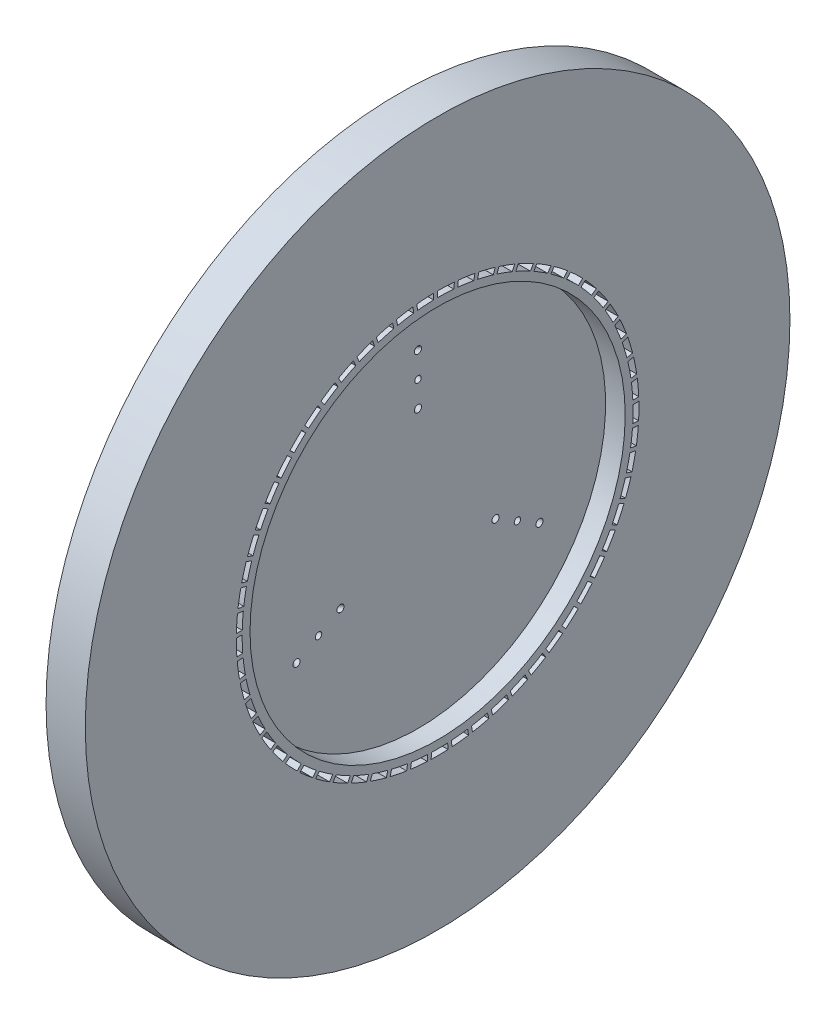
SolidWorks part; units mm, degrees
ref_plane "Front Plane" through (0, 0, 0) normal (0, 0, 1) x (1, 0, 0)
ref_plane "Top Plane" through (0, 0, 0) normal (0, 1, 0) x (1, 0, 0)
ref_plane "Right Plane" through (0, 0, 0) normal (1, 0, 0) x (0, 0, -1)
sketch "Sketch1" plane through (0, 0, 0) normal (1, 0, 0) x (0, 0, -1)
  circle A0 centre (0, 0) radius 89.825
  circle A5 centre (0, 0) radius 47.825
  dimension "D1" = 179.65
  dimension "D2" = 95.65
extrude "Flange" add sketch "Sketch1" along normal blind 10
sketch "Regen Slots Sketch" plane through (10, 0, 0) normal (1, 0, 0) x (0, 0, -1)
  line L0 (0, 49.825) -> (0, 51.325)
  line L1 (-1, 49.815) -> (-1, 51.3153)
  line L2 (5.1231, 49.5609) -> (5.2773, 51.053)
  line L3 (4.1273, 49.6538) -> (4.2816, 51.1461)
  line L4 (10.1918, 48.7715) -> (10.4986, 50.2398)
  line L5 (9.2109, 48.9662) -> (9.5178, 50.4348)
  line L6 (15.1525, 47.4651) -> (15.6087, 48.894)
  line L7 (14.1968, 47.7596) -> (14.6531, 49.1888)
  line L8 (19.9526, 45.6555) -> (20.5533, 47.03)
  line L9 (19.0323, 46.0467) -> (19.6331, 47.4215)
  line L10 (24.5412, 43.362) -> (25.28, 44.6674)
  line L11 (23.666, 43.8458) -> (24.4049, 45.1515)
  line L12 (28.8697, 40.6088) -> (29.7388, 41.8313)
  line L13 (28.0488, 41.18) -> (28.9181, 42.4028)
  line L14 (32.8921, 37.4251) -> (33.8823, 38.5518)
  line L15 (32.1343, 38.0778) -> (33.1247, 39.2047)
  line L16 (36.5658, 33.8448) -> (37.6667, 34.8637)
  line L17 (35.8792, 34.5719) -> (36.9802, 35.591)
  line L18 (39.852, 29.9057) -> (41.0517, 30.806)
  line L19 (39.2437, 30.6995) -> (40.4437, 31.6)
  line L20 (42.7157, 25.6496) -> (44.0017, 26.4217)
  line L21 (42.1923, 26.5017) -> (43.4785, 27.274)
  line L22 (45.1266, 21.1215) -> (46.4852, 21.7574)
  line L23 (44.6936, 22.023) -> (46.0524, 22.659)
  line L24 (47.0592, 16.3696) -> (48.4759, 16.8624)
  line L25 (46.7212, 17.3108) -> (48.1382, 17.8037)
  line L26 (48.4929, 11.4442) -> (49.9528, 11.7887)
  line L27 (48.2534, 12.4152) -> (49.7136, 12.7597)
  line L28 (49.4126, 6.3974) -> (50.9002, 6.59)
  line L29 (49.2742, 7.3879) -> (50.7621, 7.5805)
  line L30 (49.8085, 1.2829) -> (51.308, 1.3215)
  line L31 (49.7727, 2.2823) -> (51.2725, 2.3209)
  line L32 (49.6764, -3.8453) -> (51.1719, -3.961)
  line L33 (49.7436, -2.8475) -> (51.2394, -2.9633)
  line L34 (49.0177, -8.9327) -> (50.4934, -9.2016)
  line L35 (49.1871, -7.9471) -> (50.6631, -8.216)
  line L36 (47.8395, -13.9254) -> (49.2797, -14.3446)
  line L37 (48.1093, -12.9624) -> (49.5498, -13.3817)
  line L38 (46.1541, -18.7705) -> (47.5436, -19.3356)
  line L39 (46.5215, -17.8404) -> (47.9113, -18.4056)
  line L40 (43.9795, -23.4166) -> (45.3035, -24.1216)
  line L41 (44.4406, -22.5292) -> (45.7649, -23.2343)
  line L42 (41.3387, -27.8145) -> (42.5832, -28.6519)
  line L43 (41.8886, -26.9792) -> (43.1333, -27.8167)
  line L44 (38.2596, -31.9176) -> (39.4115, -32.8784)
  line L45 (38.8925, -31.1432) -> (40.0446, -32.1043)
  line L46 (34.7751, -35.6823) -> (35.822, -36.7565)
  line L47 (35.4842, -34.9772) -> (36.5313, -36.0516)
  line L48 (30.9219, -39.0688) -> (31.8528, -40.2449)
  line L49 (31.6998, -38.4403) -> (32.6309, -39.6167)
  line L50 (26.7409, -42.0411) -> (27.5459, -43.3068)
  line L51 (27.5793, -41.496) -> (28.3845, -42.7619)
  line L52 (22.2764, -44.5678) -> (22.9471, -45.9095)
  line L53 (23.1664, -44.1117) -> (23.8372, -45.4537)
  line L54 (17.5759, -46.6221) -> (18.105, -48.0257)
  line L55 (18.508, -46.2599) -> (19.0373, -47.6638)
  line L56 (12.689, -48.1822) -> (13.071, -49.6327)
  line L57 (13.6535, -47.9178) -> (14.0355, -49.3686)
  line L58 (7.6676, -49.2315) -> (7.8984, -50.7136)
  line L59 (8.6541, -49.0677) -> (8.885, -50.5501)
  line L60 (2.5649, -49.7589) -> (2.6421, -51.2569)
  line L61 (3.5631, -49.6974) -> (3.6403, -51.1957)
  line L62 (-2.5649, -49.7589) -> (-2.6421, -51.2569)
  line L63 (-1.5657, -49.8004) -> (-1.643, -51.2987)
  line L64 (-7.6676, -49.2315) -> (-7.8984, -50.7136)
  line L65 (-6.678, -49.3755) -> (-6.9088, -50.8579)
  line L66 (-12.689, -48.1822) -> (-13.071, -49.6327)
  line L67 (-11.7194, -48.4271) -> (-12.1015, -49.8779)
  line L68 (-17.5759, -46.6221) -> (-18.105, -48.0257)
  line L69 (-16.6366, -46.9655) -> (-17.1658, -48.3693)
  line L70 (-22.2764, -44.5678) -> (-22.9471, -45.9095)
  line L71 (-21.3775, -45.0059) -> (-22.0482, -46.3479)
  line L72 (-26.7409, -42.0411) -> (-27.5459, -43.3068)
  line L73 (-25.8917, -42.5693) -> (-26.6969, -43.8353)
  line L74 (-30.9219, -39.0688) -> (-31.8528, -40.2449)
  line L75 (-30.1315, -39.6815) -> (-31.0626, -40.8579)
  line L76 (-34.7751, -35.6823) -> (-35.822, -36.7565)
  line L77 (-34.0519, -36.373) -> (-35.099, -37.4475)
  line L78 (-38.2596, -31.9176) -> (-39.4115, -32.8784)
  line L79 (-37.6113, -32.679) -> (-38.7634, -33.6401)
  line L80 (-41.3387, -27.8145) -> (-42.5832, -28.6519)
  line L81 (-40.7721, -28.6386) -> (-42.0168, -29.4761)
  line L82 (-43.9795, -23.4166) -> (-45.3035, -24.1216)
  line L83 (-43.5006, -24.2946) -> (-44.8249, -24.9997)
  line L84 (-46.1541, -18.7705) -> (-47.5436, -19.3356)
  line L85 (-45.7681, -19.693) -> (-47.1578, -20.2582)
  line L86 (-47.8395, -13.9254) -> (-49.2797, -14.3446)
  line L87 (-47.5503, -14.8827) -> (-48.9909, -15.302)
  line L88 (-49.0177, -8.9327) -> (-50.4934, -9.2016)
  line L89 (-48.8286, -9.9147) -> (-50.3046, -10.1836)
  line L90 (-49.6764, -3.8453) -> (-51.1719, -3.961)
  line L91 (-49.5892, -4.8415) -> (-51.085, -4.9573)
  line L92 (-49.8085, 1.2829) -> (-51.308, 1.3215)
  line L93 (-49.8242, 0.283) -> (-51.324, 0.3216)
  line L94 (-49.4126, 6.3974) -> (-50.9002, 6.59)
  line L95 (-49.531, 5.4044) -> (-51.0189, 5.5971)
  line L96 (-48.4929, 11.4442) -> (-49.9528, 11.7887)
  line L97 (-48.7128, 10.4686) -> (-50.173, 10.8132)
  line L98 (-47.0592, 16.3696) -> (-48.4759, 16.8624)
  line L99 (-47.3782, 15.4218) -> (-48.7953, 15.9147)
  line L100 (-45.1266, 21.1215) -> (-46.4852, 21.7574)
  line L101 (-45.5414, 20.2116) -> (-46.9003, 20.8476)
  line L102 (-42.7157, 25.6496) -> (-44.0017, 26.4217)
  line L103 (-43.2219, 24.7871) -> (-44.5081, 25.5594)
  line L104 (-39.852, 29.9057) -> (-41.0517, 30.806)
  line L105 (-40.4442, 29.0998) -> (-41.6442, 30.0003)
  line L106 (-36.5658, 33.8448) -> (-37.6667, 34.8637)
  line L107 (-37.2377, 33.1041) -> (-38.3388, 34.1232)
  line L108 (-32.8921, 37.4251) -> (-33.8823, 38.5518)
  line L109 (-33.6366, 36.7575) -> (-34.627, 37.8844)
  line L110 (-28.8697, 40.6088) -> (-29.7388, 41.8313)
  line L111 (-29.6789, 40.0212) -> (-30.5482, 41.244)
  line L112 (-24.5412, 43.362) -> (-25.28, 44.6674)
  line L113 (-25.4065, 42.8607) -> (-26.1455, 44.1664)
  line L114 (-19.9526, 45.6555) -> (-20.5533, 47.03)
  line L115 (-20.8649, 45.2458) -> (-21.4657, 46.6206)
  line L116 (-15.1525, 47.4651) -> (-15.6087, 48.894)
  line L117 (-16.1021, 47.1514) -> (-16.5584, 48.5806)
  line L118 (-10.1918, 48.7715) -> (-10.4986, 50.2398)
  line L119 (-11.1686, 48.5571) -> (-11.4755, 50.0257)
  line L120 (-5.1231, 49.5609) -> (-5.2773, 51.053)
  line L121 (-6.1167, 49.4481) -> (-6.271, 50.9405)
  circle A0 centre (0, 0) radius 49.825
  circle A1 centre (0, 0) radius 51.325
  circle A2 centre (0, 0) radius 47.825 construction
  point P253 (0, 0)
  dimension "D2" = 1.5
  dimension "D3" = 2
  dimension "D4" = 61
extrude "Regen Slots" cut sketch "Regen Slots Sketch" against normal blind 25 contours L117 A1 L114 A0 | L119 A1 L116 A0 | L121 A1 L118 A0 | L1 A1 L120 A0 | L3 A1 L0 A0 | L5 A1 L2 A0 | L7 A1 L4 A0 | L9 A1 L6 A0 | L11 A1 L8 A0 | L13 A1 L10 A0 | L15 A1 L12 A0 | L17 A1 L14 A0 | L19 A1 L16 A0 | L21 A1 L18 A0 | L23 A1 L20 A0 | L25 A1 L22 A0 | L27 A1 L24 A0 | L29 A1 L26 A0 | L31 A1 L28 A0 | L33 A1 L30 A0 | L35 A1 L32 A0 | L37 A1 L34 A0 | L39 A1 L36 A0 | L41 A1 L38 A0 | L43 A1 L40 A0 | L45 A1 L42 A0 | L47 A1 L44 A0 | L49 A1 L46 A0 | L51 A1 L48 A0 | L53 A1 L50 A0 | L55 A1 L52 A0 | L57 A1 L54 A0 | L59 A1 L56 A0 | L61 A1 L58 A0 | L63 A1 L60 A0 | L65 A1 L62 A0 | L67 A1 L64 A0 | L69 A1 L66 A0 | L71 A1 L68 A0 | L73 A1 L70 A0 | L75 A1 L72 A0 | L77 A1 L74 A0 | L79 A1 L76 A0 | L81 A1 L78 A0 | L83 A1 L80 A0 | L85 A1 L82 A0 | L87 A1 L84 A0 | L89 A1 L86 A0 | L91 A1 L88 A0 | L93 A1 L90 A0 | L95 A1 L92 A0 | L97 A1 L94 A0 | L99 A1 L96 A0 | L101 A1 L98 A0 | L103 A1 L100 A0 | L107 A1 L104 A0 | L109 A1 L106 A0 | L111 A1 L108 A0 | L113 A1 L110 A0 | L115 A1 L112 A0 | L105 A1 L102 A0
sketch "Faceplate Extrusion to Manifold Sketch" plane through (0, 0, 0) normal (-1, 0, 0) x (0, 0, 1)
  circle A0 centre (0, 0) radius 47.825
  dimension "D1" = 95.65
extrude "Faceplate Extrusion to Manifold" add sketch "Faceplate Extrusion to Manifold Sketch" against normal blind 5 separate body
sketch "Faceplate Extrusion to Chamber Sketch" plane through (0, 0, 0) normal (-1, 0, 0) x (0, 0, 1)
  circle A0 centre (0, 0) radius 47.825
  dimension "D1" = 95.65
extrude "Faceplate Extrusion to Chamber" add sketch "Faceplate Extrusion to Chamber Sketch" along normal blind 1
sketch "O-Ring Slot Sketch" plane through (-1, 0, 0) normal (-1, 0, 0) x (0, 0, 1)
  circle A0 centre (0, 0) radius 47.825
  circle A1 centre (0, 0) radius 44.825
  dimension "D1" = 95.65
  dimension "D2" = 3
extrude "O-Ring Slot" cut sketch "O-Ring Slot Sketch" against normal blind 2.5
sketch "Fuel Orifices Sketch" plane through (-1, 0, 0) normal (-1, 0, 0) x (0, 0, 1)
  circle A0 centre (0, 32.2826) radius 0.9146 construction
  circle A1 centre (0, 29.2826) radius 0.8262
  circle A2 centre (0, 26.2826) radius 0.9146 construction
  circle A3 centre (22.7614, -13.1413) radius 0.9146 construction
  circle A4 centre (25.3595, -14.6413) radius 0.8262
  circle A5 centre (27.9576, -16.1413) radius 0.9146 construction
  circle A6 centre (-22.7614, -13.1413) radius 0.9146 construction
  circle A7 centre (-25.3595, -14.6413) radius 0.8262
  circle A8 centre (-27.9576, -16.1413) radius 0.9146 construction
  point P22 (0, 0)
  dimension "D1" = 1.8292
  dimension "D2" = 1.6524
  dimension "D5" = 29.2826
  dimension "D3" = 3
  dimension "D4" = 3
  dimension "D6" = 3
extrude "Fuel Orifices" cut sketch "Fuel Orifices Sketch" against normal through all
ref_plane "Orifice Ref Plane 1" through (0, 0, 0) normal (0, 0.866, 0.5) x (1, 0, 0)
sketch "Ox1 Guide Curve" plane through (0, 0, 0) normal (0, 0.866, 0.5) x (1, 0, 0)
  line L0 (-1, -32.2826) -> (5, -35.7467)
  line L2 (5, -47.825) -> (5, 47.825) construction
  line L5 (-1, -29.2826) -> (5, -29.2826) construction
  line L6 (-1, -28.4564) -> (-1, -30.1088) construction
  line L7 (5, -30.1088) -> (5, -28.4564) construction
  dimension "D1" = 30
sketch "Ox1 Profile" plane through (-1, 0, 0) normal (-1, 0, 0) x (0, 0, 1)
  line L0 (56.2638, -32.4839) -> (-56.2638, 32.4839) construction
  circle A0 centre (27.9576, -16.1413) radius 0.9146
  dimension "D2" = 3
  dimension "D1" = 1.8292
sweep "Ox1 Orifice 1" cut profiles "Ox1 Profile" path "Ox1 Guide Curve"
pattern_circular "Revolve Ox Orifice 1" count 3 over 360 about axis through (5, 0, 0) along (-1, 0, 0) of "Ox1 Orifice 1"
sketch "Ox2 Profile" plane through (-1, 0, 0) normal (-1, 0, 0) x (0, 0, 1)
  line L0 (56.2638, -32.4839) -> (-56.2638, 32.4839) construction
  circle A0 centre (22.7614, -13.1413) radius 0.9146
  dimension "D2" = 3
  dimension "D1" = 1.8292
sketch "Ox2 Guide Curve" plane through (0, 0, 0) normal (0, 0.866, 0.5) x (1, 0, 0)
  line L0 (-1, -26.2826) -> (5, -22.8185)
  line L1 (-1, -25.368) -> (-1, -27.1972) construction
  line L2 (5, -47.825) -> (5, 47.825) construction
  line L3 (-1, -26.2826) -> (5, -26.2826) construction
  dimension "D1" = 30
sweep "Ox Orifice 2" cut profiles "Ox2 Profile" path "Ox2 Guide Curve"
pattern_circular "Revolve Ox Orifice 2" count 3 over 360 about axis through (5, 0, 0) along (-1, 0, 0) of "Ox Orifice 2"
equation "\"Flange_Dia\"= 179.65"
equation "\"D1@Sketch1\"=\"Flange_Dia\""
equation "\"Regen_Thickness\"= 1.5"
equation "\"Regen_To_Inner\"=2"
equation "\"Faceplate_Area\"=95.65"
equation "\"Regen_Rib_Thickness\"=1"
equation "\"D2@Sketch1\"=\"Faceplate_Area\""
equation "\"Flange_Thickness\"= 10"
equation "\"D1@Flange\" = \"Flange_Thickness\""
equation "\"D1@Regen Slots Sketch\" = \"Regen_Rib_Thickness\""
equation "\"D2@Regen Slots Sketch\" = \"Regen_Thickness\""
equation "\"D3@Regen Slots Sketch\" = \"Regen_To_Inner\""
equation "\"D1@Faceplate Extrusion to Manifold Sketch\" = \"Faceplate_Area\""
equation "\"D1@Faceplate Extrusion to Chamber Sketch\" = \"Faceplate_Area\""
equation "\"Faceplate_To_Chamber_Extrusion\"=1"
equation "\"D1@Faceplate Extrusion to Chamber\"=\"Faceplate_To_Chamber_Extrusion\""
equation "\"D1@O-Ring Slot Sketch\" = \"Faceplate_Area\""
equation "\"Injector_MCCN_O-Ring\"=3"
equation "\"D2@O-Ring Slot Sketch\" = \"Injector_MCCN_O-Ring\""
equation "\"D1@O-Ring Slot\" =  ( \"Faceplate_To_Chamber_Extrusion\" )  +  ( \"Injector_MCCN_O-Ring\" / 2 ) "
equation "\"Ox_Orifice\" = 1.829247371"
equation "\"D1@Fuel Orifices Sketch\" = \"Ox_Orifice\""
equation "\"Fuel_Orifice\"= 1.65242067"
equation "\"D2@Fuel Orifices Sketch\" = \"Fuel_Orifice\""
equation "\"OxFuel_Dist_Downstream\"= 3"
equation "\"Fuel_Dist_From_Center\"=29.2826"
equation "\"D5@Fuel Orifices Sketch\" = \"Fuel_Dist_From_Center\""
equation "\"D3@Fuel Orifices Sketch\" = \"OxFuel_Dist_Downstream\""
equation "\"D4@Fuel Orifices Sketch\" = \"OxFuel_Dist_Downstream\""
equation "\"D1@Ox1 Profile\" = \"Ox_Orifice\""
equation "\"D1@Ox2 Profile\" = \"Ox_Orifice\""
equation "\"OxFuel_HalfAngle\"=30"
equation "\"D1@Ox2 Guide Curve\" = \"OxFuel_HalfAngle\""
equation "\"D2@Ox1 Profile\" = \"OxFuel_Dist_Downstream\""
equation "\"D2@Ox2 Profile\"=\"OxFuel_Dist_Downstream\""
equation "\"D1@Ox1 Guide Curve\"=\"OxFuel_HalfAngle\""
equation "\"Thickness_FuelMan\"=5"
equation "\"D1@Faceplate Extrusion to Manifold\"=\"Thickness_FuelMan\""
equation "\"OxFuel_Dist_Upstream\"=(((\"Thickness_FuelMan\" + \"Faceplate_To_Chamber_Extrusion\")*tan(\"OxFuel_HalfAngle\")))+(\"OxFuel_Dist_Downstream\")"
